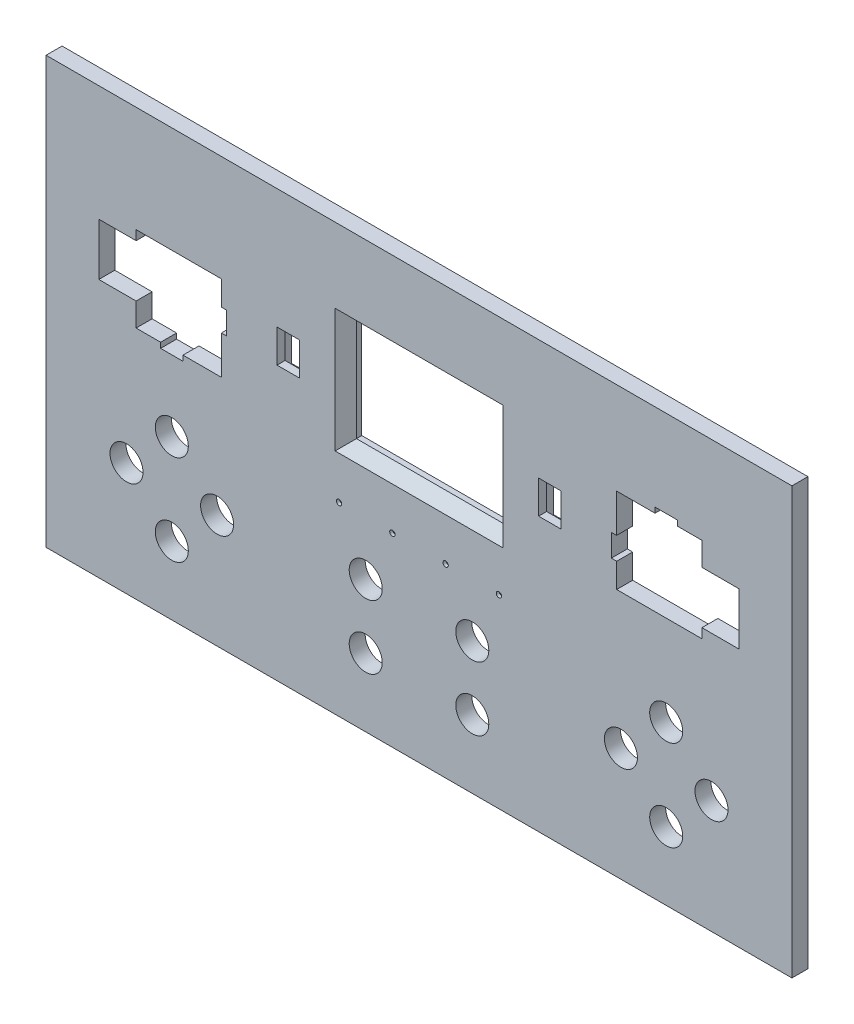
SolidWorks part; units mm, degrees
ref_plane "前视基准面" through (0, 0, 0) normal (0, 0, 1) x (1, 0, 0)
ref_plane "上视基准面" through (0, 0, 0) normal (0, 1, 0) x (1, 0, 0)
ref_plane "右视基准面" through (0, 0, 0) normal (1, 0, 0) x (0, 0, -1)
other "Configuration Table"
sketch "草图1" plane through (0, 0, 0) normal (0, 0, 1) x (1, 0, 0)
  line L1 (-70, 40) -> (70, 40)
  line L2 (-70, 40) -> (-70, -40)
  line L3 (-70, -40) -> (70, -40)
  line L4 (70, 40) -> (70, -40)
  point P4 (0, 40)
  point P6 (-70, 0)
  dimension "D1" = 140
  dimension "D2" = 80
extrude "凸台-拉伸1" add sketch "草图1" along normal blind 3
sketch "草图2" plane through (0, 0, 3) normal (0, 0, 1) x (1, 0, 0)
  line L1 (-13.75, 24) -> (13.75, 24)
  line L2 (-13.75, 24) -> (-13.75, 4.8)
  line L3 (-13.75, 4.8) -> (13.75, 4.8)
  line L4 (13.75, 24) -> (13.75, 4.8)
  line L5 (70, 40) -> (-70, 40) construction
  point P4 (0, 24)
  dimension "D1" = 27.5
  dimension "D2" = 19.2
  dimension "D3" = 16
extrude "切除-拉伸1" cut sketch "草图2" against normal through all
ref_plane "基准面1" through (0, -5.2, 0) normal (0, 1, 0) x (1, 0, 0)
chamfer "倒角1" distance 2 angle 45 4 edges at (13.75, 14.4, 3) (0, 24, 3) (0, 4.8, 3) (-13.75, 14.4, 3)
sketch "草图3" plane through (0, -5.2, 0) normal (0, 1, 0) x (1, 0, 0)
  line L0 (-15, 6.0122) -> (-15, -8.0142) construction
  line L1 (-15, -3) -> (-14.5, -3)
  line L2 (-15, -3) -> (-15, -2)
  line L3 (-15, -2) -> (-14.5, -2)
  line L4 (-14.5, -3) -> (-14.5, -2)
  line L5 (-5, 6.4208) -> (-5, -10.2476) construction
  line L6 (5, -10.0569) -> (5, -6.8431) construction
  line L7 (15, -4.2829) -> (15, -10.4382) construction
  line L8 (-15, -5.6016) -> (-5, -5.6016)
  line L9 (-5, -5.6016) -> (5, -5.6016)
  line L10 (5, -5.6016) -> (15, -5.6016)
  line L11 (70, -3) -> (-70, -3) construction
  line L12 (-15, 0.7) -> (-15, -2)
  line L13 (-5, -3) -> (-4.5, -3)
  line L14 (-5, -3) -> (-5, -2)
  line L15 (-5, -2) -> (-4.5, -2)
  line L16 (-4.5, -3) -> (-4.5, -2)
  line L17 (5, -3) -> (5.5, -3)
  line L18 (5, -3) -> (5, -2)
  line L19 (5, -2) -> (5.5, -2)
  line L20 (5.5, -3) -> (5.5, -2)
  line L21 (15, -3) -> (15.5, -3)
  line L22 (15, -3) -> (15, -2)
  line L23 (15, -2) -> (15.5, -2)
  line L24 (15.5, -3) -> (15.5, -2)
  line L25 (-5, 0.7) -> (-5, -2)
  line L26 (5, 0.7) -> (5, -2)
  line L27 (15, 0.7) -> (15, -2)
  line L28 (-16.6, -0.9) -> (-16.6, 0)
  line L29 (70, 0) -> (-70, 0) construction
  line L30 (-13.4, -0.9) -> (-13.4, 0)
  line L31 (-6.6, -0.9) -> (-6.6, 0)
  line L32 (-3.4, -0.9) -> (-3.4, 0)
  line L33 (3.4, -0.9) -> (3.4, 0)
  line L34 (6.6, -0.9) -> (6.6, 0)
  line L35 (13.4, -0.9) -> (13.4, 0)
  line L36 (16.6, -0.9) -> (16.6, 0)
  line L37 (-16.6, 0) -> (16.6, 0)
  circle A0 centre (-15, -0.9) radius 1.6
  circle A1 centre (-5, -0.9) radius 1.6
  circle A2 centre (5, -0.9) radius 1.6
  circle A3 centre (15, -0.9) radius 1.6
  point P14 (0, -5.6016)
  point P34 (-15, -2.5)
  dimension "D4" = 3.2
  dimension "D1" = 10
  dimension "D2" = 1
  dimension "D3" = 0.5
revolve "切除-旋转4" cut sketch "草图3" angle 360 about L0 region at (-14.7437, -5.2, 2.7362) region at (-14.757, -5.2, 2.2374) region at (-14.2538, -5.2, 1.0452) region at (-13.4817, -5.2, 0.2209)
revolve "切除-旋转5" cut sketch "草图3<6>" angle 360 about L5 region at (-4.7437, -5.2, 2.7362) region at (-4.757, -5.2, 2.2374) region at (-4.2538, -5.2, 1.0452) region at (-3.4817, -5.2, 0.2209)
sketch "草图3<6>" plane through (0, -5.2, 0) normal (0, 1, 0) x (1, 0, 0) same geometry as "草图3"
revolve "切除-旋转6" cut sketch "草图3<7>" angle 360 about L6 region at (5.2563, -5.2, 2.7362) region at (5.243, -5.2, 2.2374) region at (5.7462, -5.2, 1.0452) region at (6.5183, -5.2, 0.2209)
sketch "草图3<7>" plane through (0, -5.2, 0) normal (0, 1, 0) x (1, 0, 0) same geometry as "草图3"
revolve "切除-旋转7" cut sketch "草图3<8>" angle 360 about L7 region at (15.2563, -5.2, 2.7362) region at (15.243, -5.2, 2.2374) region at (15.7462, -5.2, 1.0452) region at (16.5183, -5.2, 0.2209)
sketch "草图3<8>" plane through (0, -5.2, 0) normal (0, 1, 0) x (1, 0, 0) same geometry as "草图3"
sketch "草图5" plane through (0, 0, 3) normal (0, 0, 1) x (1, 0, 0)
  line L0 (-13.75, 24) -> (-13.75, 4.8) construction
  line L1 (-26.65, 17.5) -> (-22.45, 17.5)
  line L2 (-26.65, 17.5) -> (-26.65, 11.3)
  line L3 (-26.65, 11.3) -> (-22.45, 11.3)
  line L4 (-22.45, 17.5) -> (-22.45, 11.3)
  line L7 (-26.9, 18.85) -> (-22.2, 18.85)
  line L8 (-26.9, 18.85) -> (-26.9, 9.95)
  line L9 (-26.9, 9.95) -> (-22.2, 9.95)
  line L10 (-22.2, 18.85) -> (-22.2, 9.95)
  line L11 (13.75, 4.8) -> (13.75, 24) construction
  line L12 (22.45, 11.3) -> (26.65, 11.3)
  line L13 (22.45, 11.3) -> (22.45, 17.5)
  line L14 (22.45, 17.5) -> (26.65, 17.5)
  line L15 (26.65, 11.3) -> (26.65, 17.5)
  line L16 (22.2, 9.95) -> (26.9, 9.95)
  line L17 (22.2, 9.95) -> (22.2, 18.85)
  line L18 (22.2, 18.85) -> (26.9, 18.85)
  line L19 (26.9, 9.95) -> (26.9, 18.85)
  point P6 (-13.75, 14.4)
  point P7 (-22.45, 14.4)
  point P10 (-24.55, 17.5)
  point P16 (-26.9, 14.4)
  point P17 (-26.65, 14.4)
  point P18 (-24.55, 18.85)
  point P26 (22.45, 14.4)
  point P27 (22.2, 14.4)
  point P28 (24.55, 17.5)
  point P29 (24.55, 18.85)
  dimension "D1" = 4.2
  dimension "D2" = 6.2
  dimension "D3" = 4.7
  dimension "D4" = 8.9
  dimension "D5" = 8.7
  dimension "D6" = 8.7
extrude "切除-拉伸3" cut sketch "草图5" against normal through all contours L8 L9 L10 L7 | L16 L19 L18 L17
extrude "凸台-拉伸2" add sketch "草图5<4>" against normal blind 1.5 contours L3 L4 L1 L2 | L9 L10 L7 L8 | L16 L19 L18 L17 | L12 L15 L14 L13
sketch "草图5<4>" plane through (0, 0, 3) normal (0, 0, 1) x (1, 0, 0) same geometry as "草图5"
sketch "草图7" plane through (0, 0, 3) normal (0, 0, 1) x (1, 0, 0)
  line L0 (-46.4, -10.2) -> (-46.4, -27.2)
  line L1 (37.9, -18.7) -> (54.9, -18.7)
  line L2 (-54.9, -18.7) -> (-37.9, -18.7)
  line L3 (-10, -15.2) -> (10, -15.2)
  line L4 (-37.9, -18.7) -> (37.9, -18.7)
  line L6 (-70, 40) -> (-70, -40) construction
  line L8 (-15, -5.2) -> (15, -5.2)
  line L9 (-10, -15.2) -> (-10, -5.2)
  line L10 (0, 4.8) -> (0, -5.2)
  line L11 (-13.75, 4.8) -> (13.75, 4.8) construction
  circle A0 centre (-46.4, -10.2) radius 3.1
  circle A1 centre (-46.4, -27.2) radius 3.1
  circle A2 centre (-54.9, -18.7) radius 3.1
  circle A3 centre (-37.9, -18.7) radius 3.1
  circle A4 centre (-10, -15.2) radius 3.1
  circle A5 centre (10, -15.2) radius 3.1
  circle A6 centre (-10, -27.2) radius 3.1
  circle A7 centre (10, -27.2) radius 3.1
  circle A8 centre (46.4, -10.2) radius 3.1
  circle A9 centre (37.9, -18.7) radius 3.1
  circle A10 centre (54.9, -18.7) radius 3.1
  circle A11 centre (46.4, -27.2) radius 3.1
  circle A12 centre (-15, -5.2) radius 0.5 construction
  circle A13 centre (15, -5.2) radius 0.5 construction
  point P24 (-46.4, -18.7)
  point P25 (0, -15.2)
  point P26 (46.4, -18.7)
  point P27 (-46.4, -18.7)
  point P28 (0, -18.7)
  dimension "D1" = 6.2
  dimension "D2" = 12
  dimension "D3" = 17
  dimension "D4" = 23.6
  dimension "D5" = 20
extrude "切除-拉伸5" cut sketch "草图7" against normal through all contours A0 | A2 | A1 | A3 | A6 | A4 | A5 | A7 | A9 | A8 | A10 | A11
sketch "草图8" plane through (0, 0, 3) normal (0, 0, 1) x (1, 0, 0)
  line L1 (-60.1, 18.3) -> (-53.1, 18.3)
  line L2 (-60.1, 18.3) -> (-60.1, 8.5)
  line L3 (-60.1, 8.5) -> (-53.1, 8.5)
  line L4 (-53.1, 18.3) -> (-53.1, 8.5)
  line L5 (-70, 40) -> (-70, -40) construction
  line L6 (-53.1, 20.1) -> (-37.1, 20.1)
  line L7 (-53.1, 20.1) -> (-53.1, 4.1)
  line L8 (-53.1, 4.1) -> (-37.1, 4.1)
  line L9 (-37.1, 20.1) -> (-37.1, 4.1)
  line L10 (70, 40) -> (-70, 40) construction
  line L11 (70, -40) -> (70, 40) construction
  line L12 (-37.1, 15.5) -> (-36.1, 15.5)
  line L13 (-37.1, 15.5) -> (-37.1, 11.3)
  line L14 (-37.1, 11.3) -> (-36.1, 11.3)
  line L15 (-36.1, 15.5) -> (-36.1, 11.3)
  line L16 (-44.3, 4.1) -> (-48.5, 4.1)
  line L17 (-44.3, 4.1) -> (-44.3, 3.1)
  line L18 (-44.3, 3.1) -> (-48.5, 3.1)
  line L19 (-48.5, 4.1) -> (-48.5, 3.1)
  line L20 (53.1, 6.7) -> (37.1, 6.7)
  line L21 (53.1, 6.7) -> (53.1, 22.7)
  line L22 (53.1, 22.7) -> (37.1, 22.7)
  line L23 (37.1, 6.7) -> (37.1, 22.7)
  line L24 (53.1, 18.3) -> (60.1, 18.3)
  line L25 (53.1, 18.3) -> (53.1, 8.5)
  line L26 (53.1, 8.5) -> (60.1, 8.5)
  line L27 (60.1, 18.3) -> (60.1, 8.5)
  line L28 (37.1, 15.5) -> (36.1, 15.5)
  line L29 (37.1, 15.5) -> (37.1, 11.3)
  line L30 (37.1, 11.3) -> (36.1, 11.3)
  line L31 (36.1, 15.5) -> (36.1, 11.3)
  line L32 (44.3, 22.7) -> (48.5, 22.7)
  line L33 (44.3, 22.7) -> (44.3, 23.7)
  line L34 (44.3, 23.7) -> (48.5, 23.7)
  line L35 (48.5, 22.7) -> (48.5, 23.7)
  dimension "D1" = 9.9
  dimension "D2" = 19.9
  dimension "D3" = 16
  dimension "D4" = 7
  dimension "D5" = 1.8
  dimension "D6" = 9.8
  dimension "D7" = 1
  dimension "D8" = 4.6
  dimension "D9" = 4.2
  dimension "D10" = 4.6
  dimension "D11" = 9.9
  dimension "D12" = 17.3
  dimension "D13" = 4.6
  dimension "D14" = 4.6
extrude "切除-拉伸6" cut sketch "草图8" against normal through all contours L3 L4 L1 L2 | L8 L9 L6 L7 | L18 L19 L16 L17 | L15 L14 L13 L12 | L26 L27 L24 L25 | L20 L23 L22 L21 | L31 L30 L29 L28 | L34 L35 L32 L33
sketch "草图9" plane through (0, 0, 0) normal (0, 0, -1) x (-1, 0, 0)
  circle A0 centre (-61.65, 21.2) radius 0.35
  circle A1 centre (-61.65, 5.6) radius 0.35
  circle A2 centre (-35.55, 21.2) radius 0.35
  circle A3 centre (-35.55, 5.6) radius 0.35
  circle A4 centre (-24.55, 22.4) radius 0.35
  circle A5 centre (-24.55, 6.4) radius 0.35
  circle A6 centre (-17.35, 26.65) radius 0.35
  circle A7 centre (-17.35, 2.15) radius 0.35
  circle A8 centre (17.35, 26.65) radius 0.35
  circle A9 centre (17.35, 2.15) radius 0.35
  circle A10 centre (24.55, 22.4) radius 0.35
  circle A11 centre (24.55, 6.4) radius 0.35
  circle A12 centre (35.55, 21.2) radius 0.35
  circle A13 centre (35.55, 5.6) radius 0.35
  circle A14 centre (61.65, 21.2) radius 0.35
  circle A15 centre (61.65, 5.6) radius 0.35
  circle A16 centre (46.4, -2.1) radius 0.35
  circle A17 centre (29.8, -18.7) radius 0.35
  circle A18 centre (46.4, -35.3) radius 0.35
  circle A19 centre (63, -18.7) radius 0.35
  circle A20 centre (-21.225, -5.2) radius 0.35
  circle A21 centre (0, -1.2) radius 0.35
  circle A22 centre (0, -9.2) radius 0.35
  circle A23 centre (21.225, -5.2) radius 0.35
  circle A24 centre (-18.1, -15.2) radius 0.35
  circle A25 centre (-18.1, -27.2) radius 0.35
  circle A26 centre (-3.5, -21.2) radius 0.35
  circle A27 centre (3.5, -21.2) radius 0.35
  circle A28 centre (18.1, -15.2) radius 0.35
  circle A29 centre (18.1, -27.2) radius 0.35
  circle A30 centre (-46.4, -2.1) radius 0.35
  circle A31 centre (-29.8, -18.7) radius 0.35
  circle A32 centre (-46.4, -35.3) radius 0.35
  circle A33 centre (-63, -18.7) radius 0.35
  dimension "D1" = 0.7
extrude "切除-拉伸7" cut sketch "草图9" against normal blind 1.5
